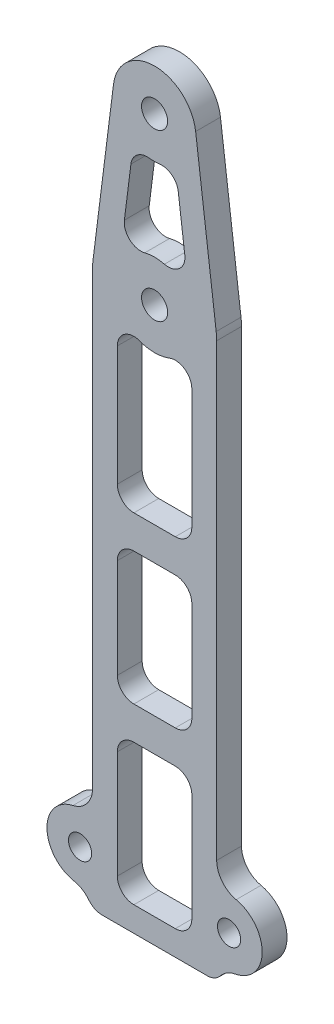
SolidWorks part; units mm, degrees
material "Thornel Mat VMA"
ref_plane "前视基准面" through (0, 0, 0) normal (0, 0, 1) x (1, 0, 0)
ref_plane "上视基准面" through (0, 0, 0) normal (0, 1, 0) x (1, 0, 0)
ref_plane "右视基准面" through (0, 0, 0) normal (1, 0, 0) x (0, 0, -1)
sketch "草图1" plane through (0, 0, 0) normal (0, 0, 1) x (1, 0, 0)
  line L0 (0, 0) -> (0, -50000) construction
  line L1 (-7.5, 0) -> (-7.5, -69.3179)
  line L2 (7.5, 0) -> (7.5, -69.3179)
  line L3 (-4.9608, 20.625) -> (-7.4412, 0.9375)
  line L4 (4.9608, 20.625) -> (7.4412, 0.9375)
  line L5 (0, -90) -> (50000, -90) construction
  line L6 (0, -90) -> (35355.3391, 35265.3391) construction
  line L7 (0, -90) -> (-35355.3391, 35265.3391) construction
  circle A0 centre (0, 0) radius 1.575
  circle A1 centre (0, -90) radius 22
  circle A2 centre (0, 0) radius 7.5
  circle A3 centre (0, 20) radius 1.575
  circle A4 centre (0, 20) radius 5
  circle A5 centre (0, -90) radius 14.5
  circle A6 centre (-12.3744, -77.6256) radius 1.575
  circle A7 centre (12.3744, -77.6256) radius 1.575
  circle A8 centre (12.3744, -102.3744) radius 1.575
  circle A9 centre (-12.3744, -102.3744) radius 1.575
  circle A10 centre (0, -90) radius 17.5 construction
  point P37 (0, -90)
  dimension "D1" = 3.15
  dimension "D2" = 44
  dimension "D4" = 3.15
  dimension "D6" = 15
  dimension "D7" = 10
  dimension "D8" = 29
  dimension "D10" = 3.15
  dimension "D3" = 90
  dimension "D5" = 20
  dimension "D9" = 45
  dimension "D11" = 35
  dimension "D12" = 4
extrude "凸台-拉伸1" add sketch "草图1" along normal blind 3 contours L0 A4 L3 A2 | L0 A4 A3 | A4 L0 A3 | A4 L0 A2 L4 | L0 A2 A0 | A2 L0 A0 | A2 L0 A1 L2 | L0 A2 L1 A1 | L0 A1 A5 | A1 L0 A5 region at (0, -37.141, 0) region at (-7.2736, 0.4564, 0) region at (0, -68.6223, 0) region at (0, 11.0094, 0) region at (0, 24.8586, 0)
sketch "草图2" plane through (0, 0, 3) normal (0, 0, 1) x (1, 0, 0)
  line L0 (0, 0) -> (0, -50000) construction
  line L1 (-2.5571, 15.7034) -> (-4.1923, 2.7249)
  line L2 (-4.9608, 20.625) -> (-7.4412, 0.9375) construction
  line L3 (-4.5, -68.4651) -> (-4.5, -2.1794)
  line L4 (-7.5, 0) -> (-7.5, -69.3179) construction
  line L5 (4.5, -68.4651) -> (4.5, -2.1794)
  line L6 (2.5571, 15.7034) -> (4.1923, 2.7249)
  circle A0 centre (0, 20) radius 5
  circle A1 centre (0, 0) radius 5
  circle A2 centre (0, -90) radius 22
  dimension "D1" = 10
  dimension "D2" = 10
  dimension "D3" = 3
  dimension "D4" = 3
extrude "切除-拉伸1" cut sketch "草图2" against normal blind 3 contours A0 L0 A1 L6 | L0 A0 L1 A1 | L0 A1 L3 A2 | A1 L0 A2 L5 region at (2.2677, -36.1727, 3) region at (-2.2677, -36.1727, 3) region at (0, 9.4049, 3)
sketch "草图3" plane through (0, 0, 3) normal (0, 0, 1) x (1, 0, 0)
  line L0 (-4.5, -25) -> (4.5, -25) construction
  line L5 (-4.5, -68.4651) -> (-4.5, -2.1794) construction
  line L6 (4.5, -68.4651) -> (4.5, -2.1794) construction
  line L7 (-4.5, -45) -> (4.5, -45) construction
  line L8 (-4.5, -47) -> (4.5, -47)
  line L9 (-4.5, -43) -> (4.5, -43)
  line L10 (-4.5, -27) -> (4.5, -27)
  line L11 (-4.5, -23) -> (4.5, -23)
  line L12 (-4.5, -23) -> (-4.5, -27)
  line L13 (4.5, -23) -> (4.5, -27)
  line L14 (-4.5, -43) -> (-4.5, -47)
  line L15 (4.5, -43) -> (4.5, -47)
  dimension "D1" = 2
  dimension "D5" = 25
  dimension "D6" = 20
  dimension "D2" = 2
  dimension "D3" = 2
  dimension "D4" = 2
extrude "凸台-拉伸2" add sketch "草图3" against normal up to surface (3 mm away) up to face at (0, -35.9111, 0)
sketch "草图4" plane through (0, 0, 3) normal (0, 0, 1) x (1, 0, 0)
  line L0 (0, 0) -> (0, -50000) construction
  circle A1 centre (-9, -61.2) radius 1.4
  circle A3 centre (-9, -61.2) radius 4
  circle A4 centre (9, -61.2) radius 4
  circle A6 centre (9, -61.2) radius 1.4
  dimension "D3" = 9
  dimension "D1" = 2.8
  dimension "D2" = 8
  dimension "D4" = 61.2
extrude "凸台-拉伸3" add sketch "草图4" against normal up to surface (3 mm away) up to face at (0, -13.2949, 0)
sketch "草图5" plane through (0, 0, 3) normal (0, 0, 1) x (1, 0, 0)
  line L0 (-25.3609, -67) -> (31.7173, -67)
  line L1 (31.7173, -67) -> (31.7173, -115.6073)
  line L2 (31.7173, -115.6073) -> (-25.3609, -115.6073)
  line L3 (-25.3609, -115.6073) -> (-25.3609, -67)
  dimension "D1" = 67
extrude "切除-拉伸2" cut sketch "草图5" against normal blind 10
sketch "草图6" plane through (0, 0, 3) normal (0, 0, 1) x (1, 0, 0)
  line L0 (-4.5, -67) -> (4.5, -67)
  line L1 (4.5, -67) -> (4.5, -64)
  line L2 (4.5, -67) -> (4.5, -47) construction
  line L3 (4.5, -64) -> (-4.5, -64)
  line L4 (-4.5, -67) -> (-4.5, -47) construction
  line L5 (-4.5, -64) -> (-4.5, -67)
  dimension "D1" = 3
extrude "凸台-拉伸4" add sketch "草图6" against normal up to surface (3 mm away) up to face at (0, -13.2949, 0)
fillet "圆角1" radius 2 14 edges at (2.5571, 15.7034, 1.5) (4.1923, 2.7249, 1.5) (-4.1923, 2.7249, 1.5) (-2.5571, 15.7034, 1.5) (-4.5, -47, 1.5) (4.5, -47, 1.5) (-4.5, -27, 1.5) (4.5, -27, 1.5) (4.5, -43, 1.5) (-4.5, -43, 1.5) (4.5, -2.1794, 1.5) (4.5, -23, 1.5) (-4.5, -23, 1.5) (-4.5, -2.1794, 1.5)
fillet "圆角2" radius 3 4 edges at (7.5, -64.9081, 1.5) (-7.5, -57.4919, 1.5) (-7.5, -64.9081, 1.5) (7.5, -57.4919, 1.5)
fillet "圆角3" radius 2 4 edges at (-7.5, -67, 1.5) (7.5, -67, 1.5) (4.5, -64, 1.5) (-4.5, -64, 1.5)
